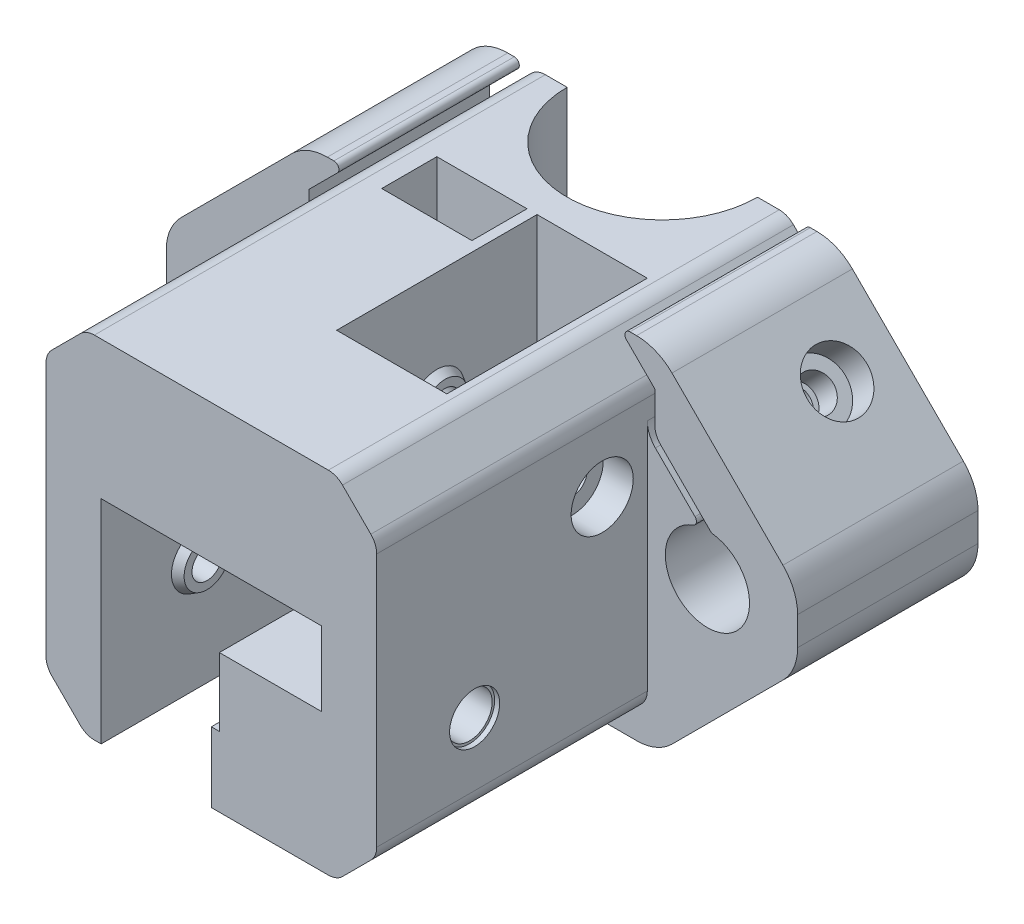
SolidWorks part; units mm, degrees
ref_plane "XY" through (0, 0, 0) normal (0, 0, 1) x (1, 0, 0)
ref_plane "XZ" through (0, 0, 0) normal (0, 1, 0) x (1, 0, 0)
ref_plane "YZ" through (0, 0, 0) normal (1, 0, 0) x (0, 0, -1)
sketch "Sketch1" plane through (0, 0, 0) normal (0, 0, 1) x (1, 0, 0)
  line L0 (-17.5, 17.5) -> (-31.5, 3.5)
  line L1 (31.5, -17.5) -> (17.5, -17.5) construction
  line L2 (31.5, -17.5) -> (31.5, -3.5) construction
  line L3 (31.5, 17.5) -> (17.5, 17.5) construction
  line L4 (-31.5, -17.5) -> (-31.5, -3.5) construction
  line L5 (31.5, -17.5) -> (-31.5, 17.5) construction
  line L6 (31.5, 17.5) -> (-31.5, -17.5) construction
  line L7 (-12.5, 17.5) -> (-16.5, 13.5)
  line L8 (-16.5, 13.5) -> (-16.5, 9.535)
  line L9 (-16.5, 9.535) -> (-21.8809, 4.1541)
  line L10 (-13.5607, 17.5) -> (-17.25, 13.8107)
  line L11 (-17.25, 13.8107) -> (-17.25, 9.8457)
  line L12 (-17.25, 9.8457) -> (-22.9163, 4.1793)
  line L13 (-17.25, 9.8457) -> (-22.4112, 4.6844) construction
  line L14 (-13.0303, 18.0303) -> (-17.25, 13.8107) construction
  line L15 (-13.5607, 17.5) -> (-17.5, 17.5)
  line L16 (0, 0) -> (-59.6161, 0) construction
  line L17 (0, 0) -> (0, 36.6742) construction
  line L18 (-17.5, -17.5) -> (-31.5, -3.5)
  line L19 (17.5, -17.5) -> (31.5, -3.5)
  line L20 (16.5, 9.535) -> (21.8809, 4.1541)
  line L21 (16.5, 13.5) -> (16.5, 9.535)
  line L22 (12.5, 17.5) -> (16.5, 13.5)
  line L23 (13.5607, 17.5) -> (17.25, 13.8107)
  line L24 (17.25, 13.8107) -> (17.25, 9.8457)
  line L25 (17.25, 9.8457) -> (22.9163, 4.1793)
  line L26 (17.5, 17.5) -> (31.5, 3.5)
  line L27 (12.5, 17.5) -> (-12.5, 17.5)
  line L28 (-17.5, 17.5) -> (-31.5, 17.5) construction
  line L29 (-31.5, 3.5) -> (-31.5, 17.5) construction
  line L30 (-31.5, -3.5) -> (-31.5, 3.5)
  line L31 (-17.5, -17.5) -> (-31.5, -17.5) construction
  line L32 (17.5, -17.5) -> (-17.5, -17.5)
  line L33 (31.5, -3.5) -> (31.5, 3.5)
  line L34 (31.5, 3.5) -> (31.5, 17.5) construction
  line L35 (17.5, 17.5) -> (13.5607, 17.5)
  arc A0 (-22.9163, 4.1793) -> (-21.8809, 4.1541) centre (-22.5, 0) ccw
  arc A1 (22.9163, 4.1793) -> (21.8809, 4.1541) centre (22.5, 0) cw
  point P0 (0, 0)
  dimension "D1" = 63
  dimension "D6" = 8.4
  dimension "D2" = 35
  dimension "D3" = 14
  dimension "D4" = 14
  dimension "D5" = 22.5
  dimension "D7" = 19
  dimension "D8" = 15
  dimension "D9" = 9.535
  dimension "D10" = 0.75
extrude "Boss-Extrude1" add sketch "Sketch1" along normal blind 18
sketch "Sketch2" plane through (0, 17.5, 0) normal (0, 1, 0) x (1, 0, 0)
  line L0 (12.5, 0) -> (-12.5, 0) construction
  line L1 (12.5, -18) -> (-12.5, -18) construction
  line L2 (-10, -18) -> (-1, -18)
  line L3 (-10, -18) -> (-10, -12.5)
  line L4 (-10, -12.5) -> (-1, -12.5)
  line L5 (-1, -18) -> (-1, -12.5)
  circle A0 centre (0, 0) radius 9.5
  point P10 (-5.5, -12.5)
  dimension "D1" = 19
  dimension "D2" = 9
  dimension "D3" = 5.5
  dimension "D4" = 5.5
extrude "Cut-Extrude1" cut sketch "Sketch2" against normal through all
fillet "Fillet1" radius 5 8 edges at (17.5, 17.5, 9) (31.5, 3.5, 9) (31.5, -3.5, 9) (17.5, -17.5, 9) (-17.5, -17.5, 9) (-31.5, -3.5, 9) (-31.5, 3.5, 9) (-17.5, 17.5, 9)
fillet "Fillet2" radius 0.5 6 edges at (-22.9163, 4.1793, 9) (-21.8809, 4.1541, 9) (21.8809, 4.1541, 9) (22.9163, 4.1793, 9) (-13.5607, 17.5, 9) (13.5607, 17.5, 9)
fillet "Fillet3" radius 2 2 edges at (17.25, 9.8457, 9) (-17.25, 9.8457, 9)
fillet "Fillet4" radius 2.75 2 edges at (-16.5, 9.535, 9) (16.5, 9.535, 9)
sketch "Sketch3" plane through (-17.5, 17.5, 0) normal (-0.7071, 0.7071, 0) x (0, 0, 1)
  line L0 (0, -2.0711) -> (0, -17.7279) construction
  circle A0 centre (6, -8.4) radius 1.75
  dimension "D1" = 3.5
  dimension "D2" = 6
  dimension "D3" = 8.4
ref_plane "Plane1" through (0, 0, 6) normal (0, 0, -1) x (-1, 0, 0)
sketch "Sketch4" plane through (0, 0, 6) normal (0, 0, -1) x (-1, 0, 0)
  line L0 (23.4397, 11.5603) -> (11.3618, -0.5176) construction
  line L1 (24.6771, 10.3229) -> (22.2023, 12.7977) construction
  line L2 (23.4397, 11.5603) -> (25.561, 9.439)
  line L3 (18.9645, 16.0355) -> (30.0355, 4.9645) construction
  line L4 (25.561, 9.439) -> (23.4397, 7.3177)
  line L5 (23.4397, 7.3177) -> (22.5558, 8.2015)
  line L6 (12.8331, 0.9537) -> (23.4397, 11.5603)
  line L9 (22.5558, 8.2015) -> (14.0705, -0.2837)
  line L10 (14.0705, -0.2837) -> (12.8331, 0.9537)
  dimension "D1" = 3
  dimension "D2" = 1.75
  dimension "D3" = 3
  dimension "D4" = 15
revolve "Cut-Revolve1" cut sketch "Sketch4" angle 360 about L0
sketch "Sketch6" plane through (-6.8934, 6.8934, 0) normal (-0.7071, 0.7071, 0) x (0, 0, 1)
  line L0 (0, -2.0711) -> (0, -17.7279) construction
  line L1 (3.425, -9.8867) -> (6, -11.3734)
  line L2 (6, -11.3734) -> (8.575, -9.8867)
  line L3 (8.575, -9.8867) -> (8.575, -6.9133)
  line L4 (8.575, -6.9133) -> (6, -5.4266)
  line L5 (6, -5.4266) -> (3.425, -6.9133)
  line L6 (3.425, -6.9133) -> (3.425, -9.8867)
  circle A0 centre (6, -8.4) radius 2.575 construction
  dimension "D1" = 5.15
extrude "Cut-Extrude2" cut sketch "Sketch6" against normal blind 15
mirror "Mirror1" about plane through (0, 0, 0) normal (1, 0, 0) of "Cut-Extrude2", "Cut-Revolve1"
sketch "Sketch7" plane through (0, 0, 0) normal (0, 0, -1) x (-1, 0, 0)
  circle A0 centre (-12.5, 12.5) radius 1.6
  dimension "D1" = 3.2
  dimension "D2" = 12.5
  dimension "D3" = 12.5
extrude "Cut-Extrude3" cut sketch "Sketch7" against normal blind 10
sketch "Sketch8" plane through (0, 0, 0) normal (0, 0, -1) x (-1, 0, 0)
  circle A0 centre (-12.5, 12.5) radius 2.35
  dimension "D1" = 4.7
extrude "Cut-Extrude4" cut sketch "Sketch8" against normal blind 5
sketch "Sketch9" plane through (0, 0, 0) normal (0, 0, -1) x (-1, 0, 0)
  circle A0 centre (-12.5, 12.5) radius 2.5
  dimension "D1" = 5
extrude "Cut-Extrude5" cut sketch "Sketch9" against normal blind 0.5
mirror "Mirror2" about plane through (0, 0, 0) normal (0, 1, 0) of "Cut-Extrude5", "Cut-Extrude4", "Cut-Extrude3"
mirror "Mirror3" about plane through (0, 0, 0) normal (1, 0, 0) of "Mirror2", "Cut-Extrude5", "Cut-Extrude4", "Cut-Extrude3"
sketch "Sketch10" plane through (0, 0, 18) normal (0, 0, 1) x (1, 0, 0)
  line L0 (12.5, 17.5) -> (-1, 17.5) construction
  line L1 (16.5, 13.5) -> (12.5, 17.5) construction
  line L2 (16.5, 10.6741) -> (16.5, 13.5) construction
  line L3 (12.5, 17.5) -> (-12.5, 17.5)
  line L4 (16.5, 13.5) -> (12.5, 17.5)
  line L5 (16.5, -13.5) -> (16.5, 13.5)
  line L6 (0, -17.5) -> (0, 17.5) construction
  line L7 (0, 0) -> (16.5, 0) construction
  line L8 (-16.5, -13.5) -> (-16.5, 13.5)
  line L9 (-16.5, 13.5) -> (-12.5, 17.5)
  line L10 (-16.5, -13.5) -> (-12.5, -17.5)
  line L11 (16.5, -13.5) -> (12.5, -17.5)
  line L12 (12.5, -17.5) -> (-12.5, -17.5)
  point P14 (-16.5, 0)
extrude "Boss-Extrude2" add sketch "Sketch10" along normal offset from surface (27 mm away) 45 up to face at (-10, -12.5, 0)
sketch "Sketch11" plane through (0, 17.5, 0) normal (0, 1, 0) x (1, 0, 0)
  line L0 (-1, -12.5) -> (-10, -12.5) construction
  line L1 (0, -12.5) -> (11, -12.5)
  line L2 (0, -12.5) -> (0, -32.5)
  line L3 (0, -32.5) -> (11, -32.5)
  line L4 (11, -12.5) -> (11, -32.5)
  dimension "D1" = 20
  dimension "D2" = 11
extrude "Cut-Extrude6" cut sketch "Sketch11" against normal blind 21.2
sketch "Sketch12" plane through (0, 0, 32.5) normal (0, 0, -1) x (-1, 0, 0)
  line L0 (0, -3.7) -> (-11, -3.7) construction
  line L1 (0, -3.7) -> (-11, -3.7)
  line L2 (0, 0) -> (-16.491, 0) construction
  line L3 (-11, -3.7) -> (-11, 3.7)
  line L4 (-11, 3.7) -> (0, 3.7)
  line L5 (0, 3.7) -> (0, -3.7)
  line L6 (0, -3.7) -> (0, -3.5912)
  line M2 (-11, 17.5) -> (-11, -3.7)
  line M3 (-11, -3.7) -> (0, -3.7)
  line M4 (0, -3.7) -> (0, 17.5)
extrude "Cut-Extrude7" cut sketch "Sketch12" against normal up to surface (12.5 mm away) contours L2 L4 M4 M2 | L5 L2 L3 M3 M4 region at (5.5, -1.85, 32.5) region at (5.5, 1.85, 32.5) up to face at (0, 0, 45)
fillet "Fillet5" radius 10 1 edges at (5.5, -3.7, 12.5)
sketch "Sketch13" plane through (0, -17.5, 0) normal (0, -1, 0) x (1, 0, 0)
  line L1 (0, 45) -> (-11, 45)
  line L2 (0, 45) -> (0, 25.2)
  line L3 (0, 25.2) -> (-11, 25.2)
  line L4 (-11, 45) -> (-11, 25.2)
  dimension "D1" = 11
  dimension "D2" = 19.8
extrude "Cut-Extrude8" cut sketch "Sketch13" against normal up to surface (21.2 mm away) up to face at (5.5, 3.7, 38.75)
fillet "Fillet6" radius 10 1 edges at (-5.5, 3.7, 25.2) tangent propagation no
sketch "Sketch14" plane through (0, 0, 45) normal (0, 0, 1) x (1, 0, 0)
  line L0 (-11, 3.7) -> (11, 3.7) construction
  line L1 (11, -3.7) -> (11, 3.7) construction
  line L2 (0, -3.7) -> (11, -3.7) construction
  line L3 (0, 3.7) -> (11, 3.7)
  line L4 (11, -3.7) -> (11, 3.7)
  line L5 (0, -3.7) -> (11, -3.7)
  line L6 (0, -3.7) -> (0, 3.7)
extrude "Cut-Extrude9" cut sketch "Sketch14" against normal up to surface (12.5 mm away) up to face at (5.5, 10.4143, 32.5)
sketch "Sketch15" plane through (-11, 0, 0) normal (1, 0, 0) x (0, 0, -1)
  circle A0 centre (-35.23, -6.365) radius 2.75
  dimension "D1" = 5.5
  dimension "D2" = 35.23
  dimension "D3" = 6.365
extrude "Boss-Extrude3" add sketch "Sketch15" along normal blind 0.8 draft 30
sketch "Sketch16" plane through (0, 0, 0) normal (-1, 0, 0) x (0, 0, 1)
  line L1 (45, -3.7) -> (31, -3.7)
  line L2 (45, -3.7) -> (45, -10.515)
  line L3 (45, -10.515) -> (31, -10.515)
  line L4 (31, -3.7) -> (31, -10.515)
  dimension "D1" = 6.815
  dimension "D2" = 14
extrude "Cut-Extrude10" cut sketch "Sketch16" against normal blind 0.8
ref_plane "Plane2" through (0, 0, 35.23) normal (0, 0, 1) x (1, 0, 0)
sketch "Sketch17" plane through (0, 0, 35.23) normal (0, 0, 1) x (1, 0, 0)
  line L0 (31.9477, -6.365) -> (-32.235, -6.365) construction
  line L2 (-11, -9.115) -> (-11, -3.615) construction
  line L3 (-11, -9.115) -> (-11, -3.615) construction
  line L4 (-16.5, -6.365) -> (-16.5, -3.265)
  line L5 (-16.5, 10.6741) -> (-16.5, -13.5) construction
  line L6 (-16.5, -3.265) -> (-13.5, -3.265)
  line L7 (-13.5, -3.265) -> (-13.5, -4.865)
  line L8 (-13.5, -4.865) -> (11.5, -4.865)
  line L9 (11.5, -4.865) -> (11.5, -4.115)
  line L10 (11.5, -4.115) -> (16, -4.115)
  line L11 (16, -4.115) -> (16, -3.865)
  line L12 (16, -3.865) -> (16.5, -3.865)
  line L13 (16.5, 13.5) -> (16.5, -13.5) construction
  line L14 (16.5, -3.865) -> (16.5, -6.365)
  line L15 (16.5, -13.5) -> (16.5, 10.6741) construction
  line L16 (16.5, -6.365) -> (-16.5, -6.365)
  point P5 (-11, -6.365)
  dimension "D1" = 3
  dimension "D2" = 3.1
  dimension "D3" = 1.5
  dimension "D4" = 2.25
  dimension "D5" = 2.5
  dimension "D6" = 0.5
  dimension "D7" = 5
revolve "Cut-Revolve2" cut sketch "Sketch17" angle 360 about L0
sketch "Sketch18" plane through (11, 0, 0) normal (-1, 0, 0) x (0, 0, 1)
  circle A0 centre (22.5, 6.365) radius 1.5
  dimension "D1" = 6.365
  dimension "D3" = 3
  dimension "D2" = 22.5
sketch "Sketch19" plane through (11, 0, 0) normal (-1, 0, 0) x (0, 0, 1)
  circle A0 centre (22.5, 6.365) radius 2.75
  dimension "D1" = 5.5
extrude "Boss-Extrude4" add sketch "Sketch19" along normal blind 0.8 draft 30
ref_plane "Plane3" through (5.5, 0, 0) normal (1, 0, 0) x (0, 0, -1)
mirror "Mirror4" about plane through (5.5, 0, 0) normal (1, 0, 0) of "Boss-Extrude4"
ref_plane "Plane4" through (0, 0, 22.5) normal (0, 0, 1) x (1, 0, 0)
sketch "Sketch20" plane through (0, 0, 22.5) normal (0, 0, 1) x (1, 0, 0)
  line L0 (11, 6.365) -> (-21.7769, 6.365) construction
  line L1 (16.5, 6.365) -> (16.5, 9.465)
  line L2 (16.5, 13.5) -> (16.5, -13.5) construction
  line L3 (16.5, 9.465) -> (13.5, 9.465)
  line L4 (13.5, 9.465) -> (13.5, 7.865)
  line L5 (13.5, 7.865) -> (-11.5, 7.865)
  line L6 (-11.5, 7.865) -> (-11.5, 8.615)
  line L7 (-11.5, 8.615) -> (-16, 8.615)
  line L8 (-16, 8.615) -> (-16, 8.865)
  line L9 (-16, 8.865) -> (-16.5, 8.865)
  line L10 (-16.5, -13.5) -> (-16.5, 13.5) construction
  line L11 (-16.5, 8.865) -> (-16.5, 6.365)
  line L12 (-16.5, 10.6741) -> (-16.5, -13.5) construction
  line L13 (-16.5, 6.365) -> (16.5, 6.365)
  dimension "D1" = 3.1
  dimension "D2" = 3
  dimension "D3" = 1.5
  dimension "D4" = 2.25
  dimension "D5" = 2.5
  dimension "D6" = 0.5
  dimension "D7" = 25
revolve "Cut-Revolve3" cut sketch "Sketch20" angle 360 about L0
fillet "Fillet7" radius 2 8 edges at (16.5, -13.5, 31.5) (12.5, -17.5, 31.5) (-12.5, -17.5, 31.5) (-16.5, -13.5, 31.5) (16.5, 13.5, 22.5) (12.5, 17.5, 22.5) (-12.5, 17.5, 22.5) (-16.5, 13.5, 22.5)
